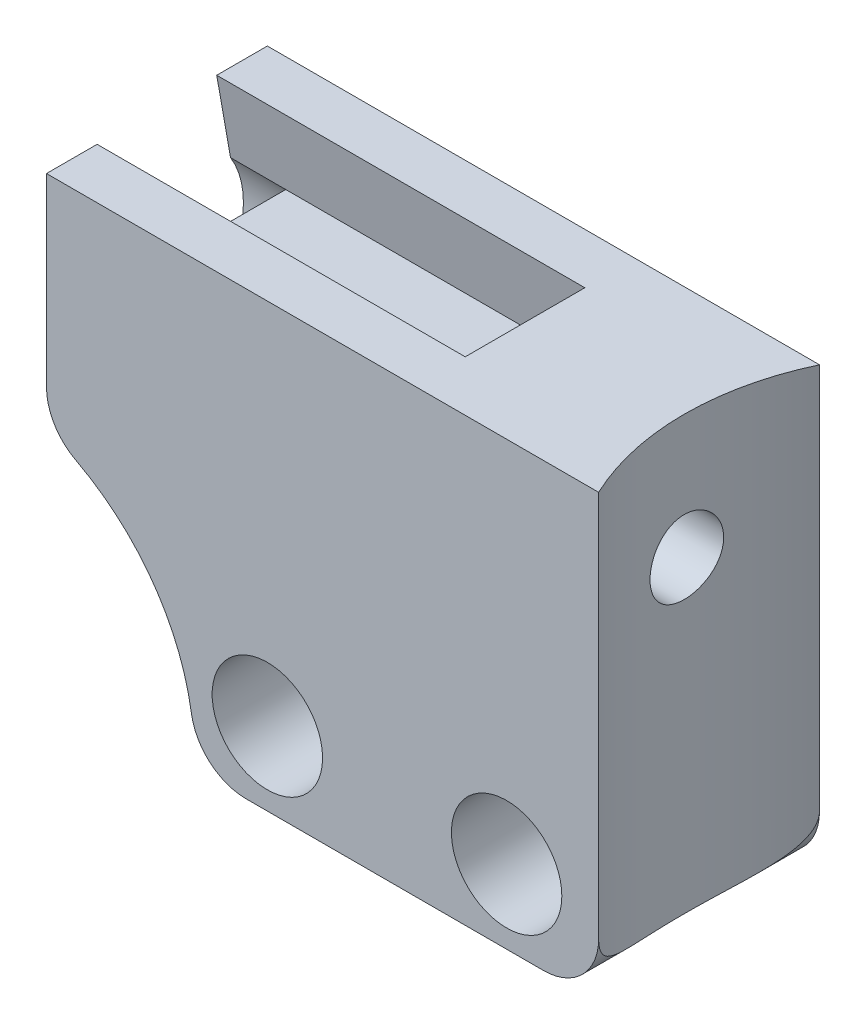
SolidWorks part; units mm, degrees
ref_plane "前视基准面" through (0, 0, 0) normal (0, 0, 1) x (1, 0, 0)
ref_plane "上视基准面" through (0, 0, 0) normal (0, 1, 0) x (1, 0, 0)
ref_plane "右视基准面" through (0, 0, 0) normal (1, 0, 0) x (0, 0, -1)
other "Configuration Table"
sketch "草图1" plane through (0, 0, 0) normal (0, 0, 1) x (1, 0, 0)
  line L0 (-19.1613, 0) -> (-3, 0)
  line L1 (0, 3) -> (0, 24)
  line L2 (0, 24) -> (-30, 24)
  line L3 (-30, 24) -> (-30, 13.9561)
  arc A0 (-28.3961, 11.3008) -> (-22.1252, 2.5359) centre (-33.9807, 0.6795) cw
  arc A1 (-19.1613, 0) -> (-22.1252, 2.5359) centre (-19.1613, 3) cw
  arc A2 (-30, 13.9561) -> (-28.3961, 11.3008) centre (-27, 13.9561) ccw
  arc A3 (-3, 0) -> (0, 3) centre (-3, 3) ccw
  circle A4 centre (-18, 4) radius 3
  circle A5 centre (-5, 4) radius 3
  point P9 (-22, 0)
  point P12 (-30, 12)
  point P15 (0, 0)
  dimension "D3" = 12
  dimension "D6" = 3
  dimension "D7" = 3
  dimension "D11" = 6
  dimension "D1" = 12
  dimension "D2" = 30
  dimension "D4" = 24
  dimension "D5" = 8
  dimension "D8" = 13
  dimension "D9" = 4
  dimension "D10" = 5
extrude "凸台-拉伸1" add sketch "草图1" along normal mid plane 12
sketch "草图2" plane through (-30, 0, 0) normal (-1, 0, 0) x (0, 0, 1)
  line L0 (0, 0) -> (0, 26.3236) construction
  line L1 (-3.25, 24) -> (3.25, 24)
  line L2 (6, 24) -> (-6, 24) construction
  line L3 (3.25, 24) -> (4, 19.7465)
  line L4 (4, 19.7465) -> (-4, 19.7465)
  line L5 (-4, 19.7465) -> (-3.25, 24)
  arc A0 (-4, 19.7465) -> (4, 19.7465) centre (0, 17.2787) ccw
  circle A1 centre (0, 17.2787) radius 2
  line M2 (-6, 13.9561) -> (6, 13.9561)
  line M4 (6, 24) -> (-6, 24)
  dimension "D4" = 4.7
  dimension "D5" = 4
  dimension "D1" = 6.5
  dimension "D2" = 8
  dimension "D3" = 80
extrude "切除-拉伸1" cut sketch "草图2" against normal through all contours L0 A1 | A1 L0 region at (-30, 17.2787, -0.8488) region at (-30, 17.2787, 0.8488)
extrude "切除-拉伸3" cut sketch "草图2<4>" against normal blind 20 contours L4 L0 L1 L5 | L0 L4 L3 M4 region at (-30, 21.7999, -1.819) region at (-30, 21.7999, 1.819)
sketch "草图2<4>" plane through (-30, 0, 0) normal (-1, 0, 0) x (0, 0, 1) same geometry as "草图2"
extrude "切除-拉伸4" cut sketch "草图2<5>" against normal blind 3 contours L0 A1 L4 A0 M2 | A0 L0 M2 | L0 A0 L4 A1 M2 | L0 A0 M2 region at (-30, 13.3976, -1.2751) region at (-30, 13.3976, 1.2751) region at (-30, 16.7992, -2.6383) region at (-30, 16.7992, 2.6383)
sketch "草图2<5>" plane through (-30, 0, 0) normal (-1, 0, 0) x (0, 0, 1) same geometry as "草图2"
sketch "草图3" plane through (0, 24, 0) normal (0, 1, 0) x (1, 0, 0)
  arc A0 (0, 6) -> (0, -6) centre (12.6491, 0) ccw
  dimension "D1" = 14
extrude "切除-拉伸5" cut sketch "草图3" against normal through all both and the other way through all
